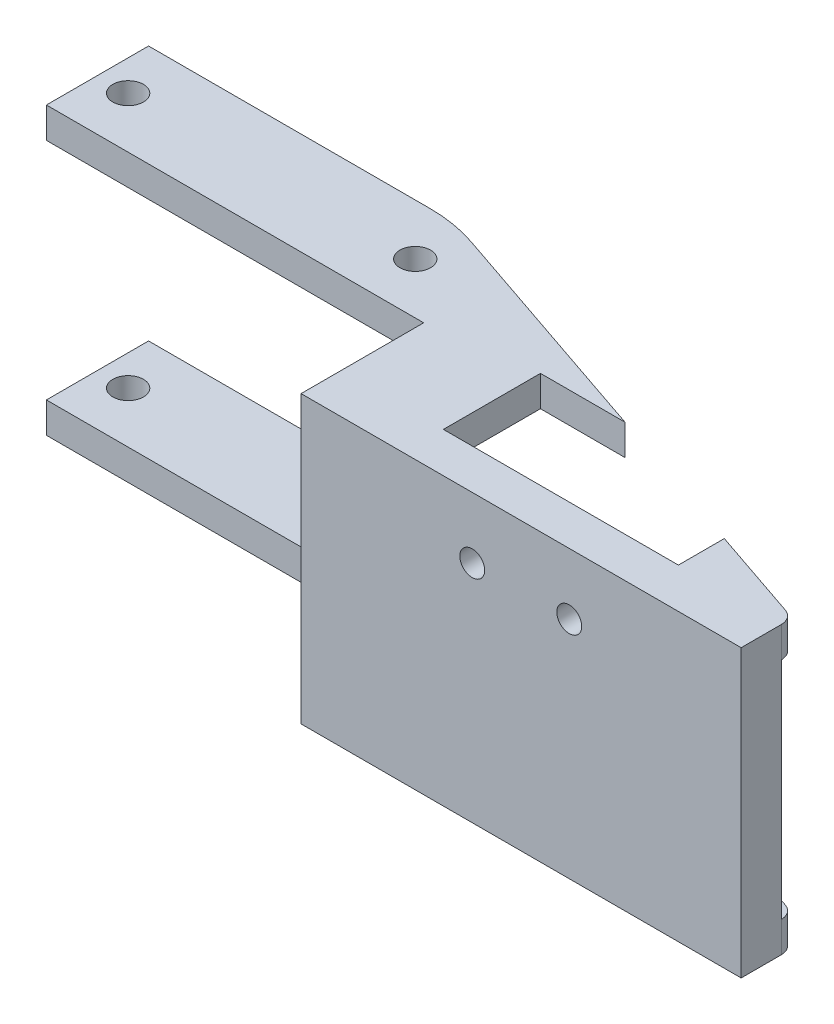
SolidWorks part; units mm, degrees
material "ABS"
ref_plane "Front Plane" through (0, 0, 0) normal (0, 0, 1) x (1, 0, 0)
ref_plane "Top Plane" through (0, 0, 0) normal (0, 1, 0) x (1, 0, 0)
ref_plane "Right Plane" through (0, 0, 0) normal (1, 0, 0) x (0, 0, -1)
sketch "Sketch1" plane through (0, 0, 0) normal (0, 1, 0) x (1, 0, 0)
  line L0 (-4.5779, 9.3563) -> (42.0567, -6.4995)
  line L1 (-36.9262, 10.1547) -> (-9.4065, 10.1547)
  line L2 (-36.9262, 10.1547) -> (-36.9262, 0.1547)
  line L3 (0, -11.8453) -> (43.0738, -11.8453)
  line L4 (43.0738, -7.9196) -> (43.0738, -11.8453)
  line L5 (-36.9262, 10.1547) -> (43.0738, -11.8453) construction
  line L6 (-3.5929, 0.1547) -> (26.2671, -1.131) construction
  line L10 (-36.9262, 0.1547) -> (0, 0.1547)
  line L11 (0, -11.8453) -> (0, 0.1547)
  arc A0 (-9.4065, 10.1547) -> (-4.5779, 9.3563) centre (-9.4065, -4.8453) cw
  arc A1 (42.0567, -6.4995) -> (43.0738, -7.9196) centre (41.5738, -7.9196) cw
  point P0 (0, 0)
  point P10 (-6.9262, 10.1547)
  point P13 (43.0738, -6.8453)
  dimension "D6" = 15
  dimension "D7" = 1.5
  dimension "D1" = 10
  dimension "D2" = 80
  dimension "D3" = 5
  dimension "D4" = 50
  dimension "D5" = 10.7143
  dimension "D8" = 12
  dimension "D9" = 33.3333
extrude "Boss-Extrude1" add sketch "Sketch1" against normal blind 3
extrude "Boss-Extrude2" add sketch "Sketch1<2>" along normal blind 3 from offset 22 separate body
sketch "Sketch1<2>" plane through (0, 0, 0) normal (0, 1, 0) x (1, 0, 0) same geometry as "Sketch1"
hole_wizard "Ø3.0mm Clearance Dowel Hole1" positions "Sketch2" profile "Sketch3" hole size "Ø3.0" standard "ANSI Metric" end condition through all
sketch "Sketch2" plane through (0, -3, 0) normal (0, -1, 0) x (-1, 0, 0)
  line L0 (36.9262, 10.1547) -> (36.9262, 0.1547) construction
  point P0 (33.9262, 5.1547)
  point P2 (5.8262, 5.1547)
  point P7 (36.9262, 5.1547)
  dimension "D1" = 3
  dimension "D2" = 28.1
sketch "Sketch3" plane through (-33.9262, -3, -5.1547) normal (1, 0, 0) x (0, 0, -1)
  line L0 (0, 0) -> (0, 28)
  line L1 (0, 28) -> (1.5, 28)
  line L2 (1.5, 28) -> (1.5, 0)
  line L5 (1.5, 0) -> (0, 0)
  line L11 (0, -6.35) -> (0, 107.95) construction
  dimension "Thru Hole Dia." = 3
  dimension "Thru Hole Depth" = 28
sketch "Sketch5" plane through (0, 0, 0) normal (0, 1, 0) x (1, 0, 0)
  line L1 (0, -11.8453) -> (43.0738, -11.8453)
  line L2 (0, -11.8453) -> (0, -7.9196)
  line L3 (0, -7.9196) -> (43.0738, -7.9196)
  line L4 (43.0738, -11.8453) -> (43.0738, -7.9196)
extrude "Boss-Extrude3" add sketch "Sketch5" along normal up to surface (22 mm away) up to face at (-33.9262, 22, -6.6547)
sketch "Sketch6" plane through (0, 25, 0) normal (0, 1, 0) x (1, 0, 0)
  line L1 (10, 1.5847) -> (33, 1.5847)
  line L2 (10, 1.5847) -> (10, -7.9153)
  line L3 (10, -7.9153) -> (33, -7.9153)
  line L4 (33, 1.5847) -> (33, -7.9153)
  line L6 (0, -11.8453) -> (43.0738, -11.8453) construction
  line L7 (0, 0.1547) -> (0, -11.8453) construction
  dimension "D1" = 23
  dimension "D2" = 9.5
  dimension "D3" = 3.93
  dimension "D4" = 10
extrude "Cut-Extrude1" cut sketch "Sketch6" against normal blind 10
sketch "Sketch7" plane through (10, 0, 0) normal (1, 0, 0) x (0, 0, -1)
  line L0 (-6.4995, 25) -> (-3.4202, 25) construction
  line L1 (-7.9153, 25) -> (1.5847, 25)
  line L2 (-7.9153, 25) -> (-7.9153, 24)
  line L3 (-7.9153, 24) -> (1.5847, 24)
  line L4 (1.5847, 25) -> (1.5847, 24)
  line L5 (-7.9153, 22) -> (-7.9153, 25) construction
  line L6 (1.5847, 22) -> (1.5847, 25) construction
  dimension "D1" = 1
extrude "Boss-Extrude4" [suppressed] add sketch "Sketch7" along normal blind 2
hole_wizard "#2 Clearance Hole1" positions "Sketch8" profile "Sketch9" hole size "#2" standard "ANSI Inch" end condition through all
sketch "Sketch8" plane through (0, 0, 11.8453) normal (0, 0, 1) x (1, 0, 0)
  line L0 (0, 25) -> (43.0738, 25) construction
  line L1 (0, -3) -> (0, 25) construction
  point P0 (16.75, 19)
  point P2 (26.25, 19)
  dimension "D1" = 6
  dimension "D2" = 9.5
  dimension "D3" = 16.75
sketch "Sketch9" plane through (16.75, 19, 11.8453) normal (1, 0, 0) x (0, -1, 0)
  line L0 (0, 0) -> (0, 22)
  line L1 (0, 22) -> (1.2192, 22)
  line L2 (1.2192, 22) -> (1.2192, 0)
  line L5 (1.2192, 0) -> (0, 0)
  line L11 (0, -6.35) -> (0, 107.95) construction
  dimension "Thru Hole Dia." = 2.4384
  dimension "Thru Hole Depth" = 22
